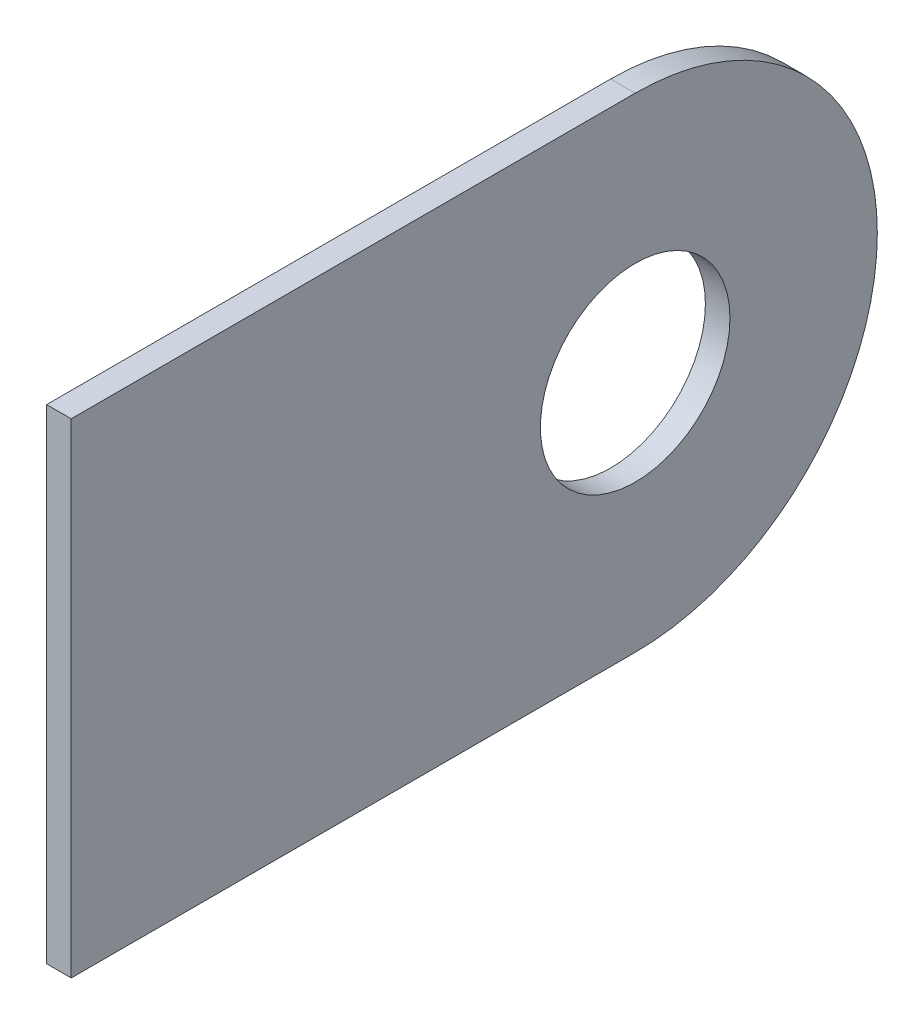
SolidWorks part; units mm, degrees
ref_plane "Front Plane" through (0, 0, 0) normal (0, 0, 1) x (1, 0, 0)
ref_plane "Top Plane" through (0, 0, 0) normal (0, 1, 0) x (1, 0, 0)
ref_plane "Right Plane" through (0, 0, 0) normal (1, 0, 0) x (0, 0, -1)
sketch "Sketch1" plane through (0, 0, 0) normal (1, 0, 0) x (0, 0, -1)
  line L0 (0, 24.65) -> (-57.407, 24.65)
  line L1 (-57.407, 24.65) -> (-57.407, -24.65)
  line L2 (-57.407, -24.65) -> (0, -24.65)
  circle A0 centre (0, 0) radius 9.65
  arc A2 (0, -24.65) -> (0, 24.65) centre (0, 0) ccw
  circle A3 centre (0, 0) radius 24.65 construction
  dimension "D1" = 19.3
  dimension "D3" = 57.407
  dimension "D2" = 15
base flange "Base-Flange1" sketch "Sketch1" thickness 2.5 reverse thickness direction no parameters "D1"=0.7366
scale "Scale1" scale about centroid uniform scaling yes scale factor 1.5
sketch "Bend-Lines1" [suppressed] plane through (0, 0, 0) normal (0, 1, 0) x (1, 0, 0)
sketch "Bounding-Box1" [suppressed] plane through (0, 0, 0) normal (0, 1, 0) x (1, 0, 0)
sheet metal parameters "Sheet-Metal1" thickness 2.5 parameters "D1"=0.7366
flat pattern "Flat-Pattern1" [suppressed]
sketch "Bend-Lines2" plane through (0, 0, 0) normal (0, 1, 0) x (1, 0, 0)
sketch3d "Bounding-Box2" [suppressed]
  line L0 (57.407, -24.65, 0) -> (-24.65, -24.65, 0) construction
  line L1 (57.407, 24.65, 0) -> (-24.65, 24.65, 0) construction
  line L2 (57.407, -24.65, 0) -> (57.407, 24.65, 0) construction
  line L3 (-24.65, -24.65, 0) -> (-24.65, 24.65, 0) construction
sheet metal parameters "Sheet-Metal2" thickness 2.5 parameters "D1"=0.7366
flat pattern "Flat-Pattern1"
sketch "Bend-Lines2" plane through (0, 0, 0) normal (0, 1, 0) x (1, 0, 0)
sketch3d "Bounding-Box2" [suppressed]
  line L0 (57.407, -24.65, 0) -> (-24.65, -24.65, 0) construction
  line L1 (57.407, 24.65, 0) -> (-24.65, 24.65, 0) construction
  line L2 (57.407, -24.65, 0) -> (57.407, 24.65, 0) construction
  line L3 (-24.65, -24.65, 0) -> (-24.65, 24.65, 0) construction
